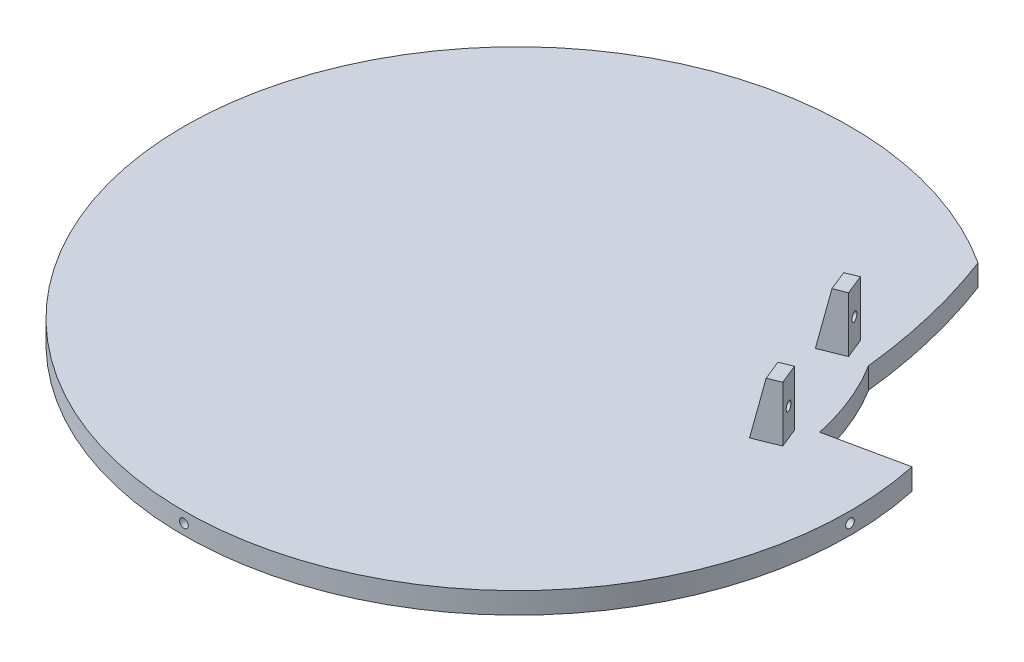
SolidWorks part; units mm, degrees
ref_plane "Front Plane" through (0, 0, 0) normal (0, 0, 1) x (1, 0, 0)
ref_plane "Top Plane" through (0, 0, 0) normal (0, 1, 0) x (1, 0, 0)
ref_plane "Right Plane" through (0, 0, 0) normal (1, 0, 0) x (0, 0, -1)
sketch "Sketch1" plane through (0, 0, 0) normal (0, -1, 0) x (1, 0, 0)
  line L0 (0, -55) -> (0, 55) construction
  line L7 (0, 0) -> (83.1425, -17.6725) construction
  line L8 (0, 0) -> (-83.1425, -17.6725) construction
  line L9 (0, 0) -> (50.8829, -31.7952) construction
  line L11 (76.589, -16.2795) -> (58.6889, -12.4747)
  arc A0 (76.589, -16.2795) -> (42.8361, -65.5435) centre (0, 0) ccw
  circle A1 centre (0, 0) radius 60 construction
  arc A4 (50.8829, -31.7952) -> (58.6889, -12.4747) centre (0, 0) ccw
  circle A5 centre (0, 0) radius 85 construction
  arc A10 (42.8361, -65.5435) -> (50.8829, -31.7952) centre (-83.1425, -17.6725) ccw
  circle A11 centre (-83.1425, -17.6725) radius 134.7675 construction
  arc A12 (38.439, -75.8119) -> (42.8361, -65.5435) centre (-83.1425, -17.6725) ccw construction
  dimension "D1" = 156.6
  dimension "D2" = 120
  dimension "D7" = 170
  dimension "D3" = 204
  dimension "D6" = 20
extrude "Boss-Extrude2" add sketch "Sketch1" along normal blind 2.5 and the other way blind 2.5 contours A0 | A10 A0 L11 A4 region at (-2.4562, 0, 1.4233)
hole_wizard "M2.5 Tapped Hole1" positions "3DSketch1" profile "Sketch2" tap size "M2.5" standard "ISO"
sketch3d "3DSketch1"
  circle A0 centre (0, 0, 0) radius 78.3 construction
  point P0 (0, 0, -78.3)
  point P3 (78.3, 0, 0)
  point P5 (0, 0, 78.3)
  point P7 (-78.3, 0, 0)
  point P31 (0, 78.3, 0)
sketch "Sketch2" plane through (0, 0, -78.3) normal (1, 0, 0) x (0, 1, 0)
  line L0 (0, 0) -> (0, 6.9659)
  line L1 (0, 6.9659) -> (1.025, 6.35)
  line L2 (1.025, 6.35) -> (1.025, 0)
  line L5 (1.025, 0) -> (0, 0)
  line L10 (0, 6.9659) -> (-1.025, 6.35) construction
  line L11 (0, -6.35) -> (0, 107.95) construction
  dimension "Tap Drill Dia." = 2.05
  dimension "Tap Drill Depth" = 6.35
  dimension "Drill Angle" = 118
sketch "Sketch3" plane through (0, 2.5, 0) normal (0, -1, 0) x (-1, 0, 0)
  line L5 (-55.3031, 9.9407) -> (-46.6871, 31.266) construction
  line L9 (0, 0) -> (-55.631, 22.4764) construction
  line L10 (-46.6871, 31.266) -> (-44.8141, 35.9019)
  line L11 (-44.8141, 35.9019) -> (-42.0326, 34.7781)
  line L12 (-42.0326, 34.7781) -> (-43.9056, 30.1422)
  line L13 (-43.9056, 30.1422) -> (-46.6871, 31.266)
  line L14 (-52.5215, 8.8169) -> (-55.3031, 9.9407)
  line L15 (-54.3946, 4.181) -> (-52.5215, 8.8169)
  line L16 (-57.1761, 5.3048) -> (-54.3946, 4.181)
  line L17 (-55.3031, 9.9407) -> (-57.1761, 5.3048)
  arc A1 (-50.8829, 31.7952) -> (-58.6889, 12.4747) centre (0, 0) ccw construction
  point P8 (-50.9951, 20.6034)
  dimension "D1" = 23
  dimension "D2" = 5
  dimension "D3" = 3
  dimension "D4" = 5
extrude "Boss-Extrude3" add sketch "Sketch3" against normal blind 13
sketch "Sketch4" plane through (50.9951, 0, -20.6034) normal (0.9272, 0, -0.3746) x (-0.3746, 0, -0.9272)
  line L0 (-11.5, 9) -> (11.5, 9) construction
  line L5 (-11.5, 15.5) -> (-11.5, 2.5) construction
  line L6 (11.5, 15.5) -> (11.5, 2.5) construction
  line L19 (-11.5, 15.5) -> (-16.5, 15.5) construction
  line L20 (-14, 15.5) -> (-14, 9) construction
  point P19 (-14, 9)
  point P21 (14, 9)
  dimension "D1" = 28
hole_wizard "M2.5 Tapped Hole2" positions "Sketch4" profile "Sketch5" tap size "M2.5" standard "ISO" end condition up to next
sketch "Sketch5" plane through (45.7506, 9, -33.5839) normal (0, 1, 0) x (-0.3746, 0, -0.9272)
  line L0 (0, 0) -> (0, 3)
  line L1 (0, 3) -> (1.025, 3)
  line L2 (1.025, 3) -> (1.025, 0)
  line L5 (1.025, 0) -> (0, 0)
  line L11 (0, -6.35) -> (0, 107.95) construction
  dimension "Thru Tap Drill Dia." = 2.05
  dimension "Thru Tap Drill Depth" = 3
chamfer "Chamfer1" distance 13 distance2 3 2 edges at (53.4581, 2.5, -6.499) (42.9691, 2.5, -32.4601) first distance on face at (53.842, 9, -5.5486) first distance on face at (43.353, 9, -31.5098)
